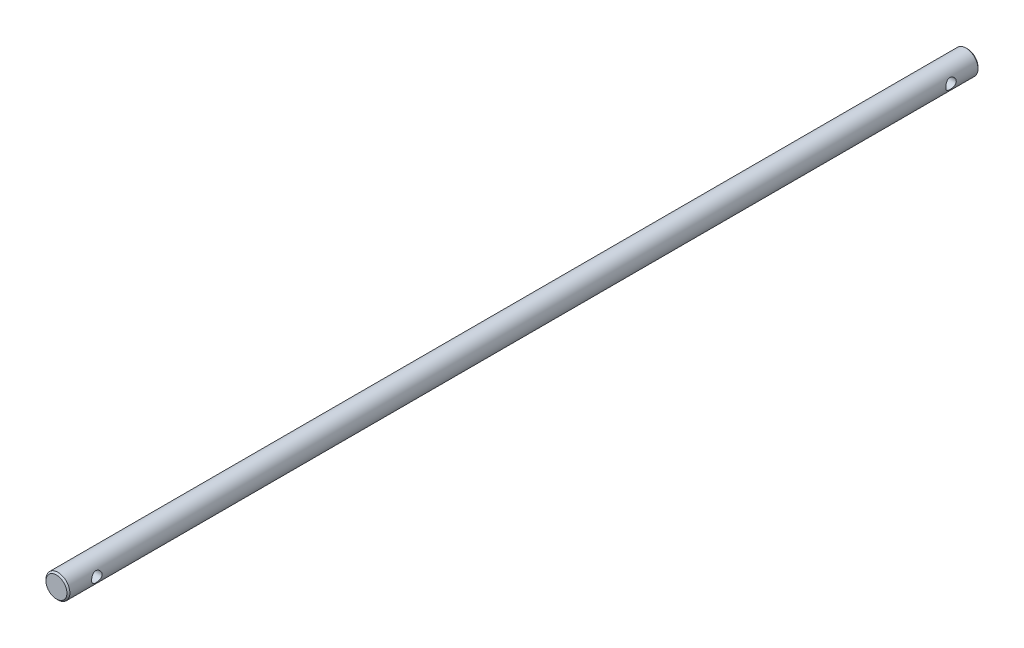
SolidWorks part; units mm, degrees
ref_plane "Front Plane" through (0, 0, 0) normal (0, 0, 1) x (1, 0, 0)
ref_plane "Top Plane" through (0, 0, 0) normal (0, 1, 0) x (1, 0, 0)
ref_plane "Right Plane" through (0, 0, 0) normal (1, 0, 0) x (0, 0, -1)
sketch "Sketch1" plane through (0, 0, 0) normal (0, 0, 1) x (1, 0, 0)
  circle A0 centre (0, 0) radius 4
  dimension "D1" = 8
extrude "Boss-Extrude1" add sketch "Sketch1" along normal blind 304.8
chamfer "Chamfer1" distance 0.5 angle 45 2 edges at (4, 0, 0) (4, 0, 304.8)
sketch "Sketch2" plane through (0, 0, 0) normal (0, 0, -1) x (-1, 0, 0)
  line L0 (-3.5, 0) -> (3.5, 0) construction
  circle A0 centre (0, 0) radius 3.5 construction
ref_plane "Plane1" through (-4, 0, 0) normal (-1, 0, 0) x (0, 0, 1)
sketch "Sketch3" plane through (-4, 0, 0) normal (-1, 0, 0) x (0, 0, 1)
  line L0 (0, 0) -> (304.8, 0) construction
  line L1 (152.4, 0) -> (152.4, -4.9674) construction
  line L2 (304.8, -3.5) -> (304.8, 3.5) construction
  circle A0 centre (9.525, 0) radius 1.7526
  circle A1 centre (295.275, 0) radius 1.7526
  dimension "D1" = 3.5052
  dimension "D2" = 9.525
extrude "Cut-Extrude1" cut sketch "Sketch3" against normal through all
